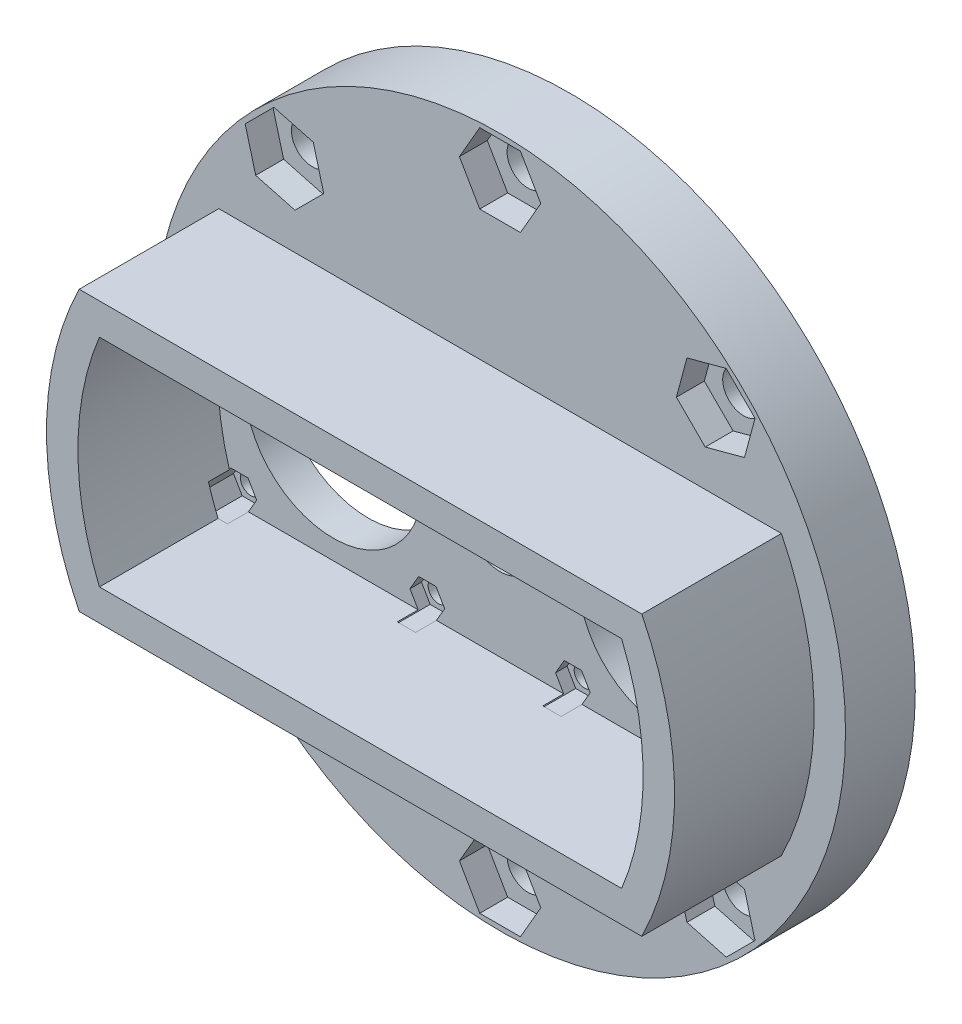
SolidWorks part; units mm, degrees
note: The reader was unsure of these and kept them because the rebuilt part matched: shared geometry of "Sketch1<12>", "Sketch1<13>".
ref_plane "Front Plane" through (0, 0, 0) normal (0, 0, 1) x (1, 0, 0)
ref_plane "Top Plane" through (0, 0, 0) normal (0, 1, 0) x (1, 0, 0)
ref_plane "Right Plane" through (0, 0, 0) normal (1, 0, 0) x (0, 0, -1)
sketch "Sketch1" plane through (0, 0, 0) normal (0, 0, 1) x (-1, 0, 0)
  line L0 (-23.9, 0) -> (-7, 0)
  line L1 (-23.9, 0) -> (-40.8, 0)
  line L3 (-7, 14.2408) -> (-7, -14.2408)
  line L6 (23.9, 0) -> (40.8, 0)
  line L8 (-40.8, 14.2408) -> (-40.8, -14.2408)
  line L11 (23.9, 0) -> (7, 0)
  line L12 (-23.9, 0) -> (-10.465, 13.435)
  line L14 (7, 14.2408) -> (7, -14.2408)
  line L18 (40.8, 14.2408) -> (40.8, -14.2408)
  line L21 (-23.9, 0) -> (-37.3704, 13.4704)
  line L22 (0, 0) -> (0, 22.2053) construction
  line L23 (0, 0) -> (0, 35) construction
  arc A0 (-40.8, -14.2408) -> (-7, -14.2408) centre (-23.9, 0) ccw
  arc A2 (7, -14.2408) -> (40.8, -14.2408) centre (23.9, 0) ccw
  arc A4 (-7, 14.2408) -> (-40.8, 14.2408) centre (-23.9, 0) ccw
  circle A5 centre (0, 0) radius 4.9
  circle A6 centre (0, 35) radius 2
  arc A7 (40.8, 14.2408) -> (7, 14.2408) centre (23.9, 0) ccw
  circle A8 centre (-37.3704, 13.4704) radius 1.5
  circle A9 centre (-10.465, 13.435) radius 1.5
  circle A10 centre (-10.465, -13.435) radius 1.5
  circle A11 centre (-37.3704, -13.4704) radius 1.5
  circle A12 centre (10.465, 13.435) radius 1.5
  circle A13 centre (10.465, -13.435) radius 1.5
  circle A14 centre (37.3704, -13.4704) radius 1.5
  circle A15 centre (37.3704, 13.4704) radius 1.5
  circle A16 centre (-23.9, 0) radius 12.7
  circle A17 centre (23.9, 0) radius 12.7
  dimension "D1" = 44.2
  dimension "D2" = 44.2
  dimension "D3" = 16.9
  dimension "D7" = 9.8
  dimension "D12" = 3
  dimension "D13" = 3
  dimension "D14" = 25.4
  dimension "D16" = 4
  dimension "D4" = 16.9
  dimension "D5" = 16.9
  dimension "D6" = 16.9
  dimension "D8" = 19
  dimension "D9" = 90
  dimension "D10" = 19.05
  dimension "D11" = 45
  dimension "D15" = 35
sketch "Sketch2" plane through (0, 0, 0) normal (0, 0, 1) x (1, 0, 0)
  circle A0 centre (0, 0) radius 49.5
  dimension "D1" = 99
extrude "Boss-Extrude1" add sketch "Sketch2" along normal blind 10
extrude "Cut-Extrude1" cut sketch "Sketch1" along normal blind 5
extrude "Cut-Extrude2" cut sketch "Sketch1<12>" along normal blind 45 contours A5 | A6 | L1 A16 L0 | L0 A16 L12 | L12 A16 L21 | L21 A16 L1 | A17 L6 L11 | A17 L11 L6
sketch "Sketch1<12>" plane through (0, 0, 0) normal (0, 0, 1) x (-1, 0, 0) same geometry as "Sketch1"
extrude "Cut-Extrude3" cut sketch "Sketch1<13>" along normal blind 10
sketch "Sketch1<13>" plane through (0, 0, 0) normal (0, 0, 1) x (-1, 0, 0) same geometry as "Sketch1"
sketch "Sketch4" plane through (0, 0, 10) normal (0, 0, 1) x (1, 0, 0)
  line L2 (0, -20) -> (0, 20)
  line L3 (-40.3113, -20) -> (40.3113, -20)
  line L5 (-40.3113, 20) -> (40.3113, 20)
  line L7 (-42.2463, -15.5) -> (42.2463, -15.5)
  line L8 (-37.4166, 15.5) -> (37.4166, 15.5)
  arc A6 (40.3113, -20) -> (40.3113, 20) centre (0, 0) ccw
  arc A7 (37.4166, -15.5) -> (37.4166, 15.5) centre (0, 0) ccw
  arc A8 (-40.3113, 20) -> (-40.3113, -20) centre (0, 0) ccw
  arc A9 (-37.4166, 15.5) -> (-37.4166, -15.5) centre (0, 0) ccw
  point P7 (0, 0)
  point P8 (0, 0)
  point P9 (0, -20)
  point P12 (0, 20)
  point P16 (0, -15.5)
  point P19 (0, 15.5)
  circle M44 centre (37.3704, -13.4704) radius 1.5
  circle M45 centre (-37.3704, 13.4704) radius 1.5
  circle M47 centre (37.3704, 13.4704) radius 1.5
  circle M48 centre (-37.3704, -13.4704) radius 1.5
  dimension "D1" = 90
  dimension "D2" = 81
  dimension "D3" = 40
  dimension "D4" = 4.5
  dimension "D5" = 4.5
extrude "Boss-Extrude2" add sketch "Sketch4" along normal blind 20 contours A9 L8 L2 L5 A8 L7 | L7 A8 L3 L2 | L3 A6 L7 L2 | A7 L7 A6 L5 L2 L8 | A9 M48 | A9 M45 | A7 M47 | A7 M44
sketch "Sketch5" plane through (0, 0, 10) normal (0, 0, 1) x (1, 0, 0)
  circle A0 centre (0, 43.7) radius 3
  circle A1 centre (30.9006, 30.9006) radius 3
  circle A3 centre (30.9006, -30.9006) radius 3
  circle A4 centre (0, -43.7) radius 3
  circle A5 centre (-30.9006, -30.9006) radius 3
  circle A7 centre (-30.9006, 30.9006) radius 3
  circle A8 centre (-43.7, 0) radius 3 [skipped]
  circle A9 centre (43.7, 0) radius 3 [skipped]
  point P19 (0, 0)
  dimension "D1" = 6
  dimension "D2" = 43.7
  dimension "D3" = 8
extrude "Cut-Extrude4" cut sketch "Sketch5" against normal blind 20
sketch "Sketch6" plane through (0, 0, 10) normal (0, 0, 1) x (1, 0, 0)
  line L0 (0, 46.7) -> (0, 40.7) construction
  line L1 (-3, 43.7) -> (3, 43.7) construction
  line L2 (33.9006, 30.9006) -> (27.9006, 30.9006) construction
  line L3 (5.8312, 43.7) -> (2.9156, 48.75)
  line L4 (2.9156, 48.75) -> (-2.9156, 48.75)
  line L5 (-2.9156, 48.75) -> (-5.8312, 43.7)
  line L6 (-5.8312, 43.7) -> (-2.9156, 38.65)
  line L7 (-2.9156, 38.65) -> (2.9156, 38.65)
  line L8 (2.9156, 38.65) -> (5.8312, 43.7)
  line L9 (30.9006, 33.9006) -> (30.9006, 27.9006) construction
  line L10 (35.0239, 26.7773) -> (36.5331, 32.4098)
  line L11 (36.5331, 32.4098) -> (32.4098, 36.5331)
  line L12 (32.4098, 36.5331) -> (26.7773, 35.0239)
  line L13 (26.7773, 35.0239) -> (25.268, 29.3913)
  line L14 (25.268, 29.3913) -> (29.3913, 25.268)
  line L15 (29.3913, 25.268) -> (35.0239, 26.7773)
  line L16 (43.7, -5.8312) -> (48.75, -2.9156)
  line L17 (48.75, -2.9156) -> (48.75, 2.9156)
  line L18 (48.75, 2.9156) -> (43.7, 5.8312)
  line L19 (43.7, 5.8312) -> (38.65, 2.9156)
  line L20 (38.65, 2.9156) -> (38.65, -2.9156)
  line L21 (38.65, -2.9156) -> (43.7, -5.8312)
  line L22 (26.7773, -35.0239) -> (32.4098, -36.5331)
  line L23 (32.4098, -36.5331) -> (36.5331, -32.4098)
  line L24 (36.5331, -32.4098) -> (35.0239, -26.7773)
  line L25 (35.0239, -26.7773) -> (29.3913, -25.268)
  line L26 (29.3913, -25.268) -> (25.268, -29.3913)
  line L27 (25.268, -29.3913) -> (26.7773, -35.0239)
  line L28 (-5.8312, -43.7) -> (-2.9156, -48.75)
  line L29 (-2.9156, -48.75) -> (2.9156, -48.75)
  line L30 (2.9156, -48.75) -> (5.8312, -43.7)
  line L31 (5.8312, -43.7) -> (2.9156, -38.65)
  line L32 (2.9156, -38.65) -> (-2.9156, -38.65)
  line L33 (-2.9156, -38.65) -> (-5.8312, -43.7)
  line L34 (-35.0239, -26.7773) -> (-36.5331, -32.4098)
  line L35 (-36.5331, -32.4098) -> (-32.4098, -36.5331)
  line L36 (-32.4098, -36.5331) -> (-26.7773, -35.0239)
  line L37 (-26.7773, -35.0239) -> (-25.268, -29.3913)
  line L38 (-25.268, -29.3913) -> (-29.3913, -25.268)
  line L39 (-29.3913, -25.268) -> (-35.0239, -26.7773)
  line L40 (-43.7, 5.8312) -> (-48.75, 2.9156)
  line L41 (-48.75, 2.9156) -> (-48.75, -2.9156)
  line L42 (-48.75, -2.9156) -> (-43.7, -5.8312)
  line L43 (-43.7, -5.8312) -> (-38.65, -2.9156)
  line L44 (-38.65, -2.9156) -> (-38.65, 2.9156)
  line L45 (-38.65, 2.9156) -> (-43.7, 5.8312)
  line L46 (-26.7773, 35.0239) -> (-32.4098, 36.5331)
  line L47 (-32.4098, 36.5331) -> (-36.5331, 32.4098)
  line L48 (-36.5331, 32.4098) -> (-35.0239, 26.7773)
  line L49 (-35.0239, 26.7773) -> (-29.3913, 25.268)
  line L50 (-29.3913, 25.268) -> (-25.268, 29.3913)
  line L51 (-25.268, 29.3913) -> (-26.7773, 35.0239)
  circle A0 centre (0, 43.7) radius 3 construction
  circle A1 centre (0, 43.7) radius 5.05 construction
  circle A2 centre (30.9006, 30.9006) radius 3 construction
  point P66 (0, 0)
  circle M7 centre (0, 43.7) radius 3
  circle M9 centre (-30.9006, -30.9006) radius 3
  circle M10 centre (0, -43.7) radius 3
  circle M11 centre (30.9006, -30.9006) radius 3
  circle M12 centre (30.9006, 30.9006) radius 3
  dimension "D1" = 8
extrude "Cut-Extrude5" cut sketch "Sketch6" against normal blind 4 contours L7 L8 L3 L4 L5 L6 M7 | L14 L15 L10 L11 L12 L13 M12 | L26 L27 L22 L23 L24 L25 M11 | L32 L33 L28 L29 L30 L31 M10 | L38 L39 L34 L35 L36 L37 M9 | L46 L47 L48 L49 L50 L51
sketch "Sketch7" plane through (0, 0, 10) normal (0, 0, 1) x (1, 0, 0)
  line L0 (-23.9, 0) -> (-23.9, 5.6651)
  line L1 (-34.8878, 13.4704) -> (-36.1291, 15.6204)
  line L2 (-36.1291, 15.6204) -> (-38.6117, 15.6204)
  line L3 (-38.6117, 15.6204) -> (-39.853, 13.4704)
  line L4 (-39.853, 13.4704) -> (-38.6117, 11.3204)
  line L5 (-38.6117, 11.3204) -> (-36.1291, 11.3204)
  line L6 (-36.1291, 11.3204) -> (-34.8878, 13.4704)
  line L7 (-23.9, 5.6651) -> (-16.6109, 0)
  line L8 (-16.6109, 0) -> (-23.9, 0)
  line L9 (-11.6709, 11.3204) -> (-12.9122, 13.4704)
  line L10 (-9.1883, 11.3204) -> (-11.6709, 11.3204)
  line L11 (-7.947, 13.4704) -> (-9.1883, 11.3204)
  line L12 (-9.1883, 15.6204) -> (-7.947, 13.4704)
  line L13 (-11.6709, 15.6204) -> (-9.1883, 15.6204)
  line L14 (-12.9122, 13.4704) -> (-11.6709, 15.6204)
  line L15 (-9.1883, -11.3204) -> (-11.6709, -11.3204)
  line L16 (-7.947, -13.4704) -> (-9.1883, -11.3204)
  line L17 (-9.1883, -15.6204) -> (-7.947, -13.4704)
  line L18 (-11.6709, -15.6204) -> (-9.1883, -15.6204)
  line L19 (-12.9122, -13.4704) -> (-11.6709, -15.6204)
  line L20 (-11.6709, -11.3204) -> (-12.9122, -13.4704)
  line L21 (-36.1291, -11.3204) -> (-34.8878, -13.4704)
  line L22 (-38.6117, -11.3204) -> (-36.1291, -11.3204)
  line L23 (-39.853, -13.4704) -> (-38.6117, -11.3204)
  line L24 (-38.6117, -15.6204) -> (-39.853, -13.4704)
  line L25 (-36.1291, -15.6204) -> (-38.6117, -15.6204)
  line L26 (-34.8878, -13.4704) -> (-36.1291, -15.6204)
  line L27 (0, 0) -> (0, 7.6032)
  line L28 (0, 7.6032) -> (0.22, 7.6032)
  line L29 (36.1291, 11.3204) -> (34.8878, 13.4704)
  line L30 (38.6117, 11.3204) -> (36.1291, 11.3204)
  line L31 (39.853, 13.4704) -> (38.6117, 11.3204)
  line L32 (38.6117, 15.6204) -> (39.853, 13.4704)
  line L33 (36.1291, 15.6204) -> (38.6117, 15.6204)
  line L34 (34.8878, 13.4704) -> (36.1291, 15.6204)
  line L35 (9.1883, 11.3204) -> (11.6709, 11.3204)
  line L36 (7.947, 13.4704) -> (9.1883, 11.3204)
  line L37 (9.1883, 15.6204) -> (7.947, 13.4704)
  line L38 (11.6709, 15.6204) -> (9.1883, 15.6204)
  line L39 (12.9122, 13.4704) -> (11.6709, 15.6204)
  line L40 (11.6709, 11.3204) -> (12.9122, 13.4704)
  line L41 (7.947, -13.4704) -> (9.1883, -11.3204)
  line L42 (9.1883, -15.6204) -> (7.947, -13.4704)
  line L43 (11.6709, -15.6204) -> (9.1883, -15.6204)
  line L44 (12.9122, -13.4704) -> (11.6709, -15.6204)
  line L45 (11.6709, -11.3204) -> (12.9122, -13.4704)
  line L46 (9.1883, -11.3204) -> (11.6709, -11.3204)
  line L47 (38.6117, -11.3204) -> (36.1291, -11.3204)
  line L48 (39.853, -13.4704) -> (38.6117, -11.3204)
  line L49 (38.6117, -15.6204) -> (39.853, -13.4704)
  line L50 (36.1291, -15.6204) -> (38.6117, -15.6204)
  line L51 (34.8878, -13.4704) -> (36.1291, -15.6204)
  line L52 (36.1291, -11.3204) -> (34.8878, -13.4704)
  circle A0 centre (-37.3704, 13.4704) radius 2.15 construction
  line M32 (37.4166, 15.5) -> (-37.4166, 15.5)
  arc M33 (-37.4166, 15.5) -> (-37.6414, 14.9457) centre (0, 0) ccw
  line M34 (-37.4166, -15.5) -> (37.4166, -15.5)
  arc M35 (37.4166, -15.5) -> (37.6414, -14.9457) centre (0, 0) ccw
extrude "Cut-Extrude6" cut sketch "Sketch7" against normal blind 1.65 and the other way blind 3 contours L5 L6 L1 L4 M32 M33 | L14 L9 L10 L11 L12 M32 | L26 L21 L22 L23 M33 M34 | L15 L20 L19 L17 L16 M34 | L46 L41 L42 L44 L45 M34 | L35 L40 L39 L37 L36 M32 | L34 L29 L30 L31 M35 M32 | L47 L52 L51 L48 M34 M35 | L3 L4 L1 L2 M33 M32 | L26 L23 L24 L25 M34 M33 | L19 L18 L17 M34 | L44 L42 L43 M34 | L51 L50 L49 L48 M34 M35 | L34 L31 L32 L33 M32 M35
